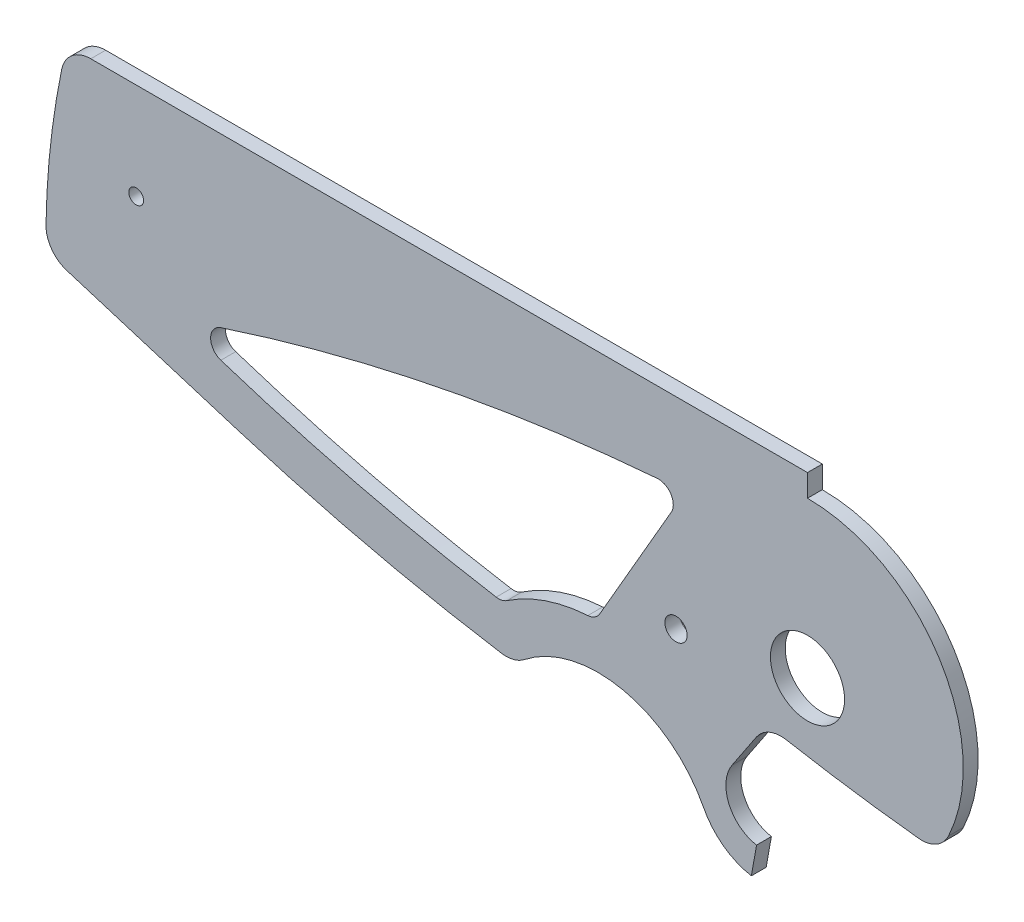
SolidWorks part; units mm, degrees
material "Obyčejná uhlíková ocel"
ref_plane "Přední rovina" through (0, 0, 0) normal (0, 0, 1) x (1, 0, 0)
ref_plane "Horní rovina" through (0, 0, 0) normal (0, 1, 0) x (1, 0, 0)
ref_plane "Pravá rovina" through (0, 0, 0) normal (1, 0, 0) x (0, 0, -1)
sketch "Skica15" plane through (0, 0, 0) normal (0, 0, 1) x (1, 0, 0)
  line L0 (0, 10) -> (0, -10)
  line L1 (0, 0) -> (-50, 0) construction
  line L2 (-1.7365, -9.8481) -> (1.7365, 9.8481)
  line L3 (0, 0) -> (49.2404, -8.6824) construction
  arc A0 (-50, 0) -> (0, 10) centre (0, -120) cw
  arc A1 (-50, 0) -> (0, -10) centre (0, 120) ccw
  arc A2 (1.7365, 9.8481) -> (49.2404, -8.6824) centre (-20.8378, -118.1769) cw
  arc A3 (-1.7365, -9.8481) -> (49.2404, -8.6824) centre (20.8378, 118.1769) ccw
  circle A4 centre (0, 0) radius 10
  dimension "D2" = 130
  dimension "D1" = 20
  dimension "D3" = 50
  dimension "D4" = 10
sketch "Skica1" plane through (0, 0, 0) normal (0, 0, 1) x (1, 0, 0)
  line L1 (-3.4519, -5.1731) -> (-5.0795, -7.6124)
  line L2 (0, 0) -> (-59.5409, 0) construction
  line L3 (-3, -9) -> (-3, -17.0212) construction
  line L4 (-3.4341, -11.462) -> (-3.7814, -13.4316)
  line L5 (-49.9157, -1.1721) -> (-38.4483, -4.7076)
  line L6 (0, 10.5) -> (0, 12)
  line L7 (0, 12) -> (-48.3078, 12)
  circle A0 centre (0, 0) radius 2.5
  arc A1 (9.5026, -4.4665) -> (0, 10.5) centre (0, 0) ccw
  arc A2 (7.478, -5.6042) -> (-1.4305, -4.3154) centre (20.8378, 118.1769) cw
  arc A3 (-5.0795, -7.6124) -> (-3.4341, -11.462) centre (-3, -9) ccw
  arc A4 (-7, -11.0616) -> (-3.7814, -13.4316) centre (-3, -9) ccw
  arc A5 (7.478, -5.6042) -> (9.5026, -4.4665) centre (7.6926, -3.6157) ccw
  arc A6 (-50.2663, 10.4054) -> (-51.3262, 0.7691) centre (0, 0) ccw
  arc A7 (-1.7365, -9.8481) -> (49.2404, -8.6824) centre (20.8378, 118.1769) ccw construction
  arc A8 (-7, -11.0616) -> (-19.0746, -8.4525) centre (-14.1111, -14.7265) ccw
  arc A9 (-51.3262, 0.7691) -> (-49.9157, -1.1721) centre (-49.3265, 0.7391) ccw
  arc A10 (-20.6316, -8.8588) -> (-38.4483, -4.7076) centre (0, 120) cw
  circle A11 centre (-50, 0) radius 1 construction
  arc A12 (-20.6316, -8.8588) -> (-19.0746, -8.4525) centre (-20.3154, -6.8839) ccw
  arc A13 (-50, 0) -> (0, -10) centre (0, 120) ccw construction
  arc A14 (-1.4305, -4.3154) -> (-3.4519, -5.1731) centre (-1.7882, -6.2832) ccw
  arc A15 (-48.3078, 12) -> (-50.2663, 10.4054) centre (-48.3078, 10) ccw
  point P18 (0, 0)
  point P34 (-19.7017, -9.0042)
  dimension "D1" = 5
  dimension "D2" = 10.5
  dimension "D3" = 2
  dimension "D4" = 5
  dimension "D5" = 3
  dimension "D6" = 9
  dimension "D7" = 2
  dimension "D10" = 2
  dimension "D11" = 2
  dimension "D13" = 2
  dimension "D14" = 12
  dimension "D12" = 2
  dimension "D9" = 0.5
  dimension "D16" = 8
  dimension "D17" = 1.5
  dimension "D19" = 2
  dimension "D15" = 2
  dimension "D8" = 10
  dimension "D18" = 7
extrude "Přidat vysunutím1" add sketch "Skica1" along normal blind 1
sketch "Skica2" plane through (0, 0, 0) normal (0, 0, 1) x (1, 0, 0)
  line L0 (-8.8633, -1.5628) -> (0, 0) construction
  line L2 (0, 0) -> (-50, 0) construction
  circle A0 centre (-8.8633, -1.5628) radius 0.75
  circle A1 centre (-45.2466, 5.5) radius 0.5
  dimension "D3" = 1.5
  dimension "D5" = 1
  dimension "D8" = 5.5
  dimension "D1" = 10
  dimension "D2" = 9
  dimension "D7" = 45.2466
sketch "Skica14" plane through (0, 0, 0) normal (0, 0, 1) x (1, 0, 0)
  line L0 (-14.001, -3.2504) -> (-9.1805, 5.0988)
  line L1 (0, 0) -> (-50, 0) construction
  arc A0 (-39.5409, -1.2137) -> (-20.9819, -5.7617) centre (0, 120) ccw
  arc A1 (-39.5422, 0.6873) -> (-10.1263, 6.5956) centre (0, -120) cw
  arc A2 (-38.4483, -4.7076) -> (-20.6316, -8.8588) centre (0, 120) ccw construction
  circle A3 centre (0, 0) radius 10 construction
  arc A4 (-39.5422, 0.6873) -> (-39.5409, -1.2137) centre (-39.2308, -0.263) ccw
  arc A5 (-20.2585, -5.6046) -> (-20.9819, -5.7617) centre (-20.8174, -4.7753) cw
  arc A6 (-9.1805, 5.0988) -> (-10.1263, 6.5956) centre (-10.0466, 5.5988) ccw
  arc A7 (0, 10) -> (-50, 0) centre (0, -120) ccw construction
  arc A8 (-20.2585, -5.6046) -> (-14.804, -3.7484) centre (-14.1111, -14.7265) cw
  arc A10 (-14.804, -3.7484) -> (-14.001, -3.2504) centre (-14.867, -2.7504) ccw
  arc A11 (-38.4483, -4.7076) -> (-20.6316, -8.8588) centre (0, 120) ccw construction
  arc A13 (-7, -11.0616) -> (-19.0746, -8.4525) centre (-14.1111, -14.7265) ccw construction
  dimension "D2" = 3
  dimension "D3" = 2
  dimension "D4" = 3
  dimension "D5" = 3
  dimension "D6" = 0.5
  dimension "D1" = 60
extrude "Odebrat vysunutím2" cut sketch "Skica2" along normal through all
extrude "Odebrat vysunutím3" cut sketch "Skica14" along normal through all
